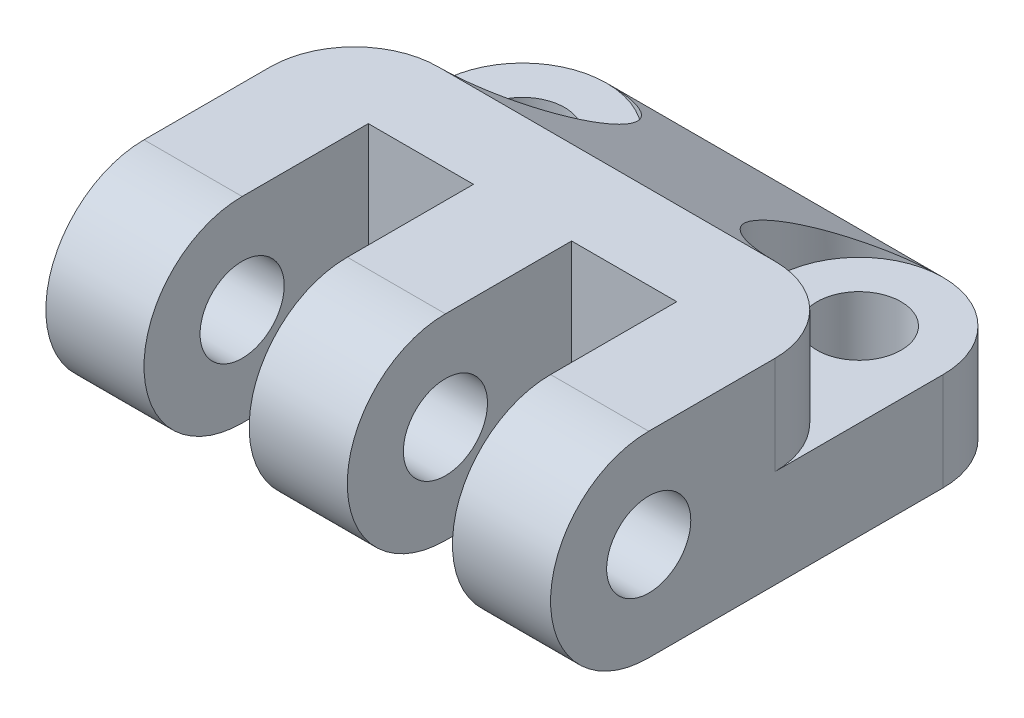
SolidWorks part; units mm, degrees
ref_plane "Front Plane" through (0, 0, 0) normal (0, 0, 1) x (1, 0, 0)
ref_plane "Top Plane" through (0, 0, 0) normal (0, 1, 0) x (1, 0, 0)
ref_plane "Right Plane" through (0, 0, 0) normal (1, 0, 0) x (0, 0, -1)
sketch "Sketch1" plane through (0, 0, 0) normal (0, 1, 0) x (1, 0, 0)
  line L1 (-9, 4.5) -> (9, 4.5)
  line L2 (-9, 4.5) -> (-9, -4.5)
  line L3 (-9, -4.5) -> (9, -4.5)
  line L4 (9, 4.5) -> (9, -4.5)
  line L5 (-9, 4.5) -> (9, -4.5) construction
  line L6 (-9, -4.5) -> (9, 4.5) construction
  point P0 (0, 0)
  dimension "D1" = 18
  dimension "D2" = 9
extrude "Boss-Extrude1" add sketch "Sketch1" along normal blind 3.5
sketch "Sketch2" plane through (0, 3.5, 0) normal (0, 1, 0) x (1, 0, 0)
  line L0 (0, 4.5) -> (0, -4.5) construction
  line L1 (9, 4.5) -> (-9, 4.5) construction
  line L2 (-9, -4.5) -> (9, -4.5) construction
  line L3 (-9, 1.5) -> (9, 1.5) construction
  line L4 (-9, 4.5) -> (-9, -4.5) construction
  line L5 (9, -4.5) -> (9, 4.5) construction
  circle A0 centre (-6, 1.5) radius 1.5
  circle A1 centre (6, 1.5) radius 1.5
  dimension "D1" = 3
  dimension "D2" = 12
  dimension "D3" = 6
extrude "Cut-Extrude1" cut sketch "Sketch2" against normal through all
sketch "Sketch4" plane through (0, 0, 0) normal (0, -1, 0) x (1, 0, 0)
  line L0 (0, 4.5) -> (0, -4.5) construction
  line L1 (-9, 4.5) -> (9, 4.5) construction
  line L2 (9, -4.5) -> (-9, -4.5) construction
  line L3 (-1.75, 12.5) -> (1.75, 12.5)
  line L4 (-6, -4.5) -> (6, -4.5)
  line L5 (-5.5, 4.5) -> (-1.75, 4.5)
  line L6 (9, 12.5) -> (9, 4.5)
  line L7 (0, 4.5) -> (0, 12.5) construction
  line L8 (5.5, 12.5) -> (9, 12.5)
  line L9 (5.5, 4.5) -> (5.5, 12.5)
  line L10 (1.75, 4.5) -> (1.75, 12.5)
  line L11 (5.5, 4.5) -> (1.75, 4.5)
  line L12 (-1.75, 4.5) -> (-1.75, 12.5)
  line L14 (-5.5, 4.5) -> (-5.5, 12.5)
  line L15 (-5.5, 12.5) -> (-9, 12.5)
  line L16 (-9, 12.5) -> (-9, 4.5)
  arc A0 (-3, -1.5) -> (-6, -4.5) centre (-6, -1.5) cw
  arc A1 (-3, -1.5) -> (-6, 1.5) centre (-6, -1.5) ccw
  arc A2 (-6, 1.5) -> (-9, 4.5) centre (-6, 4.5) cw
  arc A3 (6, 1.5) -> (9, 4.5) centre (6, 4.5) ccw
  arc A4 (3, -1.5) -> (6, 1.5) centre (6, -1.5) cw
  arc A5 (3, -1.5) -> (6, -4.5) centre (6, -1.5) ccw
  point P29 (0, 12.5)
  dimension "D1" = 3
  dimension "D2" = 3.5
  dimension "D3" = 3.75
  dimension "D4" = 8
extrude "Boss-Extrude3" add sketch "Sketch4" against normal blind 7
sketch "Sketch7" plane through (9, 0, 0) normal (1, 0, 0) x (0, 0, -1)
  line L3 (-9, 7) -> (-12.5, 7)
  line L4 (-12.5, 7) -> (-12.5, 3.5)
  line L5 (-12.5, 3.5) -> (-12.5, 0)
  line L6 (-12.5, 0) -> (-9, 0)
  arc A0 (-9, 7) -> (-9, 0) centre (-9, 3.5) ccw
extrude "Cut-Extrude3" cut sketch "Sketch7" against normal through all contours A0 L3 L4 | A0 L4 L5 | A0 L6 L5 L4 L3 region at (9, 6.2182, 11.7182) region at (9, 0.7818, 11.7182)
sketch "Sketch8" plane through (9, 0, 0) normal (1, 0, 0) x (0, 0, -1)
  circle A0 centre (-9, 3.5) radius 1.5
  arc A3 (-9, 7) -> (-9, 0) centre (-9, 3.5) ccw construction
  dimension "D1" = 3
extrude "Cut-Extrude4" cut sketch "Sketch8" against normal through all
sketch "Sketch6" plane through (9, 0, 0) normal (1, 0, 0) x (0, 0, -1)
  line L0 (-1.5, 7) -> (4.5, 3.5)
  line L1 (4.5, 3.5) -> (4.5, 7)
  line L2 (4.5, 7) -> (-1.5, 7)
fillet "Fillet1" radius 3 2 edges at (-9, 1.75, -4.5) (9, 1.75, -4.5)
extrude "Cut-Extrude5" cut sketch "Sketch6" against normal through all
move or copy body "Body-Move/Copy1" [suppressed] bodies to move or copy 108 copy no rotation origin (0, 3.5, 4) rotation axis (1, 0, 0) rotation angle 90
